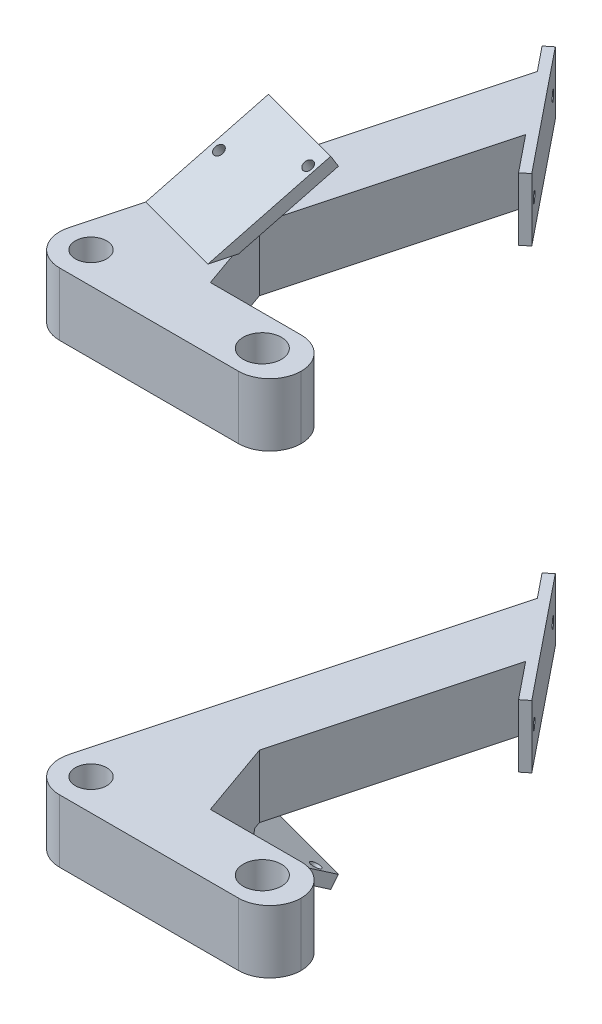
SolidWorks part; units mm, degrees
ref_plane "前视基准面" through (0, 0, 0) normal (0, 0, 1) x (1, 0, 0)
ref_plane "上视基准面" through (0, 0, 0) normal (0, 1, 0) x (1, 0, 0)
ref_plane "右视基准面" through (0, 0, 0) normal (1, 0, 0) x (0, 0, -1)
other "Configuration Table"
sketch "草图1" plane through (0, 0, 0) normal (0, 0, 1) x (1, 0, 0)
  line L1 (-50, 10) -> (50, 10)
  line L2 (-50, 10) -> (-50, -10)
  line L3 (-50, -10) -> (50, -10)
  line L4 (50, 10) -> (50, -10)
  line L5 (0, -10) -> (0, 10) construction
  line L6 (-50, 0) -> (50, 0) construction
  point P0 (0, 0)
  dimension "D1" = 20
  dimension "D2" = 100
extrude "凸台-拉伸1" add sketch "草图1" along normal blind 20
sketch "草图2" plane through (0, 10, 0) normal (0, 1, 0) x (1, 0, 0)
  circle A0 centre (37.5, -9.8805) radius 6.1
extrude "切除-拉伸1" cut sketch "草图2" against normal through all
fillet "圆角1" radius 10 1 edges at (50, 0, 20) type face fillet first side face at (50, 0, 10) second side face at (0, 0, 20)
fillet "圆角2" radius 10 1 edges at (50, 0, 0) type face fillet first side face at (50, 0, 5) second side face at (0, 0, 0)
sketch "草图4" plane through (-50, 0, 0) normal (-1, 0, 0) x (0, 0, 1)
  line L4 (0, 10) -> (0, -10)
  line L5 (0, -10) -> (20, -10)
  line L6 (20, -10) -> (20, 10)
  line L7 (20, 10) -> (0, 10)
  line L8 (0, 10) -> (0, -10)
  line L9 (0, -10) -> (20, -10)
  line L10 (20, -10) -> (20, 10)
  line L11 (20, 10) -> (0, 10)
  dimension "D1" = 0
extrude "切除-拉伸2" cut sketch "草图4" against normal blind 20
sketch "草图6" plane through (0, 10, 0) normal (0, 1, 0) x (1, 0, 0)
  line L0 (-3.9355, 0) -> (22.3864, 98.2347)
  line L1 (40, 0) -> (-30, 0) construction
  line L3 (6.8448, 117.5067) -> (-30, -20)
  line L4 (-30, -20) -> (-3.9355, 0)
  line L5 (22.3864, 98.2347) -> (6.8448, 117.5067)
  dimension "D1" = 20
  dimension "D2" = 115
  dimension "D3" = 75
extrude "凸台-拉伸2" add sketch "草图6" against normal blind 20
sketch "草图7" plane through (0, 10, 0) normal (0, 1, 0) x (1, 0, 0)
  line L0 (-24.641, 0) -> (-30, -20)
  line L1 (-30, -20) -> (-30, 0)
  line L2 (-30, 0) -> (-24.641, 0)
  line L3 (6.8448, 117.5067) -> (-24.641, 0) construction
extrude "切除-拉伸3" cut sketch "草图7" against normal through all
sketch "草图9" plane through (0, 10, 0) normal (0, 1, 0) x (1, 0, 0)
  line L0 (6.8448, 117.5067) -> (22.3864, 98.2347)
  line L1 (22.3864, 98.2347) -> (21.4253, 94.6476)
  line L2 (-3.9355, 0) -> (22.3864, 98.2347) construction
  line L3 (21.4253, 94.6476) -> (5.8836, 113.9195)
  line L4 (6.8448, 117.5067) -> (-30, -20) construction
  line L5 (5.8836, 113.9195) -> (6.8448, 117.5067)
  dimension "D1" = 3
extrude "切除-拉伸4" cut sketch "草图9" against normal through all
sketch "草图10" plane through (0, 10, 0) normal (0, 1, 0) x (1, 0, 0)
  line L0 (11.0645, 0) -> (-3.9355, 0)
  line L1 (40, 0) -> (-3.9355, 0) construction
  line L2 (-3.9355, 0) -> (2.535, 24.1481)
  line L3 (-3.9355, 0) -> (21.4253, 94.6476) construction
  line L4 (2.535, 24.1481) -> (11.0645, 0)
  dimension "D1" = 15
  dimension "D2" = 25
extrude "凸台-拉伸3" add sketch "草图10" against normal through all
sketch "草图11" plane through (0, 10, 0) normal (0, 1, 0) x (1, 0, 0)
  line L0 (0.9802, 119.9998) -> (32.2155, 81.2675)
  line L1 (32.2155, 81.2675) -> (29.8803, 79.3842)
  line L2 (29.8803, 79.3842) -> (-1.355, 118.1166)
  line L3 (-1.355, 118.1166) -> (0.9802, 119.9998)
  line L4 (5.8836, 113.9195) -> (21.4253, 94.6476) construction
  line L5 (5.8836, 113.9195) -> (-30, -20) construction
  line L6 (2.535, 24.1481) -> (21.4253, 94.6476) construction
  point P6 (4.9225, 110.3324)
  point P7 (20.4641, 91.0605)
  point P11 (20.4641, 91.0605)
  dimension "D1" = 3
  dimension "D2" = 10
  dimension "D3" = 15
extrude "凸台-拉伸4" add sketch "草图11" against normal through all
fillet "圆角3" radius 10 1 edges at (-30, 0, 20) type face fillet first side face at (-12.5388, 0, -45.1662) second side face at (5, 0, 20)
sketch "草图12" plane through (-22.9904, 0, -6.1603) normal (-0.9659, 0, -0.2588) x (-0.2588, 0, 0.9659)
  line L0 (-5.9492, 10) -> (-13.9492, 10)
  line L1 (-107.8469, 10) -> (14.0508, 10) construction
  line L2 (-13.9492, 10) -> (-39.9299, 25)
  line L3 (-39.9299, 25) -> (-37.9299, 28.4641)
  line L4 (-37.9299, 28.4641) -> (-5.9492, 10)
  line L5 (14.0508, -10) -> (14.0508, 10) construction
  dimension "D1" = 20
  dimension "D2" = 8
  dimension "D3" = 30
  dimension "D4" = 30
extrude "凸台-拉伸5" add sketch "草图12" against normal up to surface (20 mm away) up to face at (11.4995, 0, -57.6043)
sketch "草图13" plane through (-3.6719, 0, -0.9839) normal (0.9659, 0, 0.2588) x (0.2588, 0, -0.9659)
  line L4 (37.9299, 28.4641) -> (5.9492, 10)
  line L5 (5.9492, 10) -> (13.9492, 10)
  line L6 (13.9492, 10) -> (39.9299, 25)
  line L7 (39.9299, 25) -> (37.9299, 28.4641)
  line L8 (37.9299, 28.4641) -> (5.9492, 10)
  line L9 (5.9492, 10) -> (13.9492, 10)
  line L10 (13.9492, 10) -> (39.9299, 25)
  line L11 (39.9299, 25) -> (37.9299, 28.4641)
  dimension "D1" = 0
extrude "凸台-拉伸6" add sketch "草图13" along normal blind 8
sketch "草图14" plane through (-22.9904, 0, -6.1603) normal (-0.9659, 0, -0.2588) x (-0.2588, 0, 0.9659)
  line L0 (-20.8774, 14) -> (-13.9492, 10)
  line L1 (-39.9299, 25) -> (-13.9492, 10) construction
  line L2 (-13.9492, 10) -> (-21.9492, 10)
  line L3 (-107.8469, 10) -> (-13.9492, 10) construction
  line L4 (-21.9492, 10) -> (-20.8774, 14)
  dimension "D1" = 8
  dimension "D2" = 8
extrude "凸台-拉伸7" add sketch "草图14" against normal up to surface (21.3943 mm away) up to face at (6.8384, 3.3333, -11.9646)
ref_plane "基准面1" through (0, -72.7, 0) normal (0, -1, 0) x (-1, 0, 0)
mirror "镜向1" about plane through (0, -72.7, 0) normal (0, -1, 0) of bodies 116
sketch "草图15" plane through (0, -10, 0) normal (0, -1, 0) x (1, 0, 0)
  line L0 (-16.9677, 20) -> (40, 20) construction
  line L1 (4.9225, -110.3324) -> (-26.627, 7.4118) construction
  circle A0 centre (-16.9677, 10) radius 5
  dimension "D1" = 10
  dimension "D2" = 10
  dimension "D3" = 10
extrude "切除-拉伸5" cut sketch "草图15" against normal through all both and the other way through all
sketch "草图16" plane through (-17.031, -113.9739, 63.5607) normal (-0.1294, -0.866, 0.483) x (0.9916, -0.113, 0.063)
  line L0 (-4.4571, -86.0878) -> (7.6208, -98.018)
  line L1 (2.9862, -104.892) -> (27.5607, -111.315)
  line L2 (32.1161, -155.2183) -> (42.1891, -145.0206) construction
  line L5 (-4.4571, -86.0878) -> (3.8904, -122.0602) construction
  line L6 (22.8182, -79.7586) -> (-4.4571, -86.0878) construction
  circle A0 centre (2.9862, -104.892) radius 1.6
  circle A1 centre (27.5607, -111.315) radius 1.6
  dimension "D3" = 3.2
  dimension "D4" = 3.2
  dimension "D1" = 25.4
  dimension "D2" = 30
  dimension "D5" = 3
  dimension "D6" = 20
extrude "切除-拉伸6" cut sketch "草图16" against normal blind 10 and the other way through all contours A0 | A1
sketch "草图18" plane through (-0.7358, 4.9239, 2.746) normal (-0.1294, 0.866, 0.483) x (0.9916, 0.113, 0.063)
  line L0 (-20.8905, 15.2695) -> (-3.4836, 32.4636)
  line L1 (15.6827, 84.4) -> (25.7557, 74.2023) construction
  line L2 (-13.4473, 34.0737) -> (11.1272, 40.4967)
  line L3 (6.3848, 8.9403) -> (-20.8905, 15.2695) construction
  line L6 (-17.5161, 29.8114) -> (-17.7583, 28.7673) construction
  circle A0 centre (-13.4473, 34.0737) radius 1.6
  circle A1 centre (11.1272, 40.4967) radius 1.6
  dimension "D5" = 3.2
  dimension "D6" = 3.2
  dimension "D1" = 30
  dimension "D2" = 25.4
  dimension "D3" = 20
  dimension "D4" = 3
extrude "切除-拉伸7" cut sketch "草图18" against normal blind 10 contours A0 | A1 region at (10.1014, 26.6345, -33.2805) region at (-12.5409, 20.2708, -27.9365)
sketch "草图19" plane through (56.8965, 0, -45.8836) normal (-0.7784, 0, 0.6277) x (0.6277, 0, 0.7784)
  line L0 (-92.7946, 10) -> (-82.7946, 10) construction
  line L1 (-92.7946, -10) -> (-92.7946, 10) construction
  line L2 (-58.0368, 10) -> (-43.0368, 10) construction
  line L3 (-43.0368, -10) -> (-43.0368, 10) construction
  circle A0 centre (-87.7946, 0) radius 1.6
  circle A1 centre (-48.0368, 0) radius 1.6
  dimension "D1" = 3.2
  dimension "D2" = 3.2
  dimension "D3" = 10
  dimension "D4" = 5
  dimension "D5" = 10
  dimension "D6" = 5
extrude "切除-拉伸8" cut sketch "草图19" against normal blind 10
sketch "草图20" plane through (56.8965, 0, -45.8836) normal (-0.7784, 0, 0.6277) x (0.6277, 0, 0.7784)
  line L0 (-92.7946, -135.4) -> (-92.7946, -155.4) construction
  line L1 (-92.7946, -135.4) -> (-82.7946, -135.4) construction
  line L2 (-58.0368, -135.4) -> (-43.0368, -135.4) construction
  line L3 (-43.0368, -135.4) -> (-43.0368, -155.4) construction
  circle A0 centre (-87.7946, -145.4) radius 1.6
  circle A1 centre (-48.0368, -145.4) radius 1.6
  dimension "D3" = 3.2
  dimension "D4" = 3.2
  dimension "D1" = 5
  dimension "D2" = 10
  dimension "D5" = 10
  dimension "D6" = 5
extrude "切除-拉伸9" cut sketch "草图20" against normal blind 10
